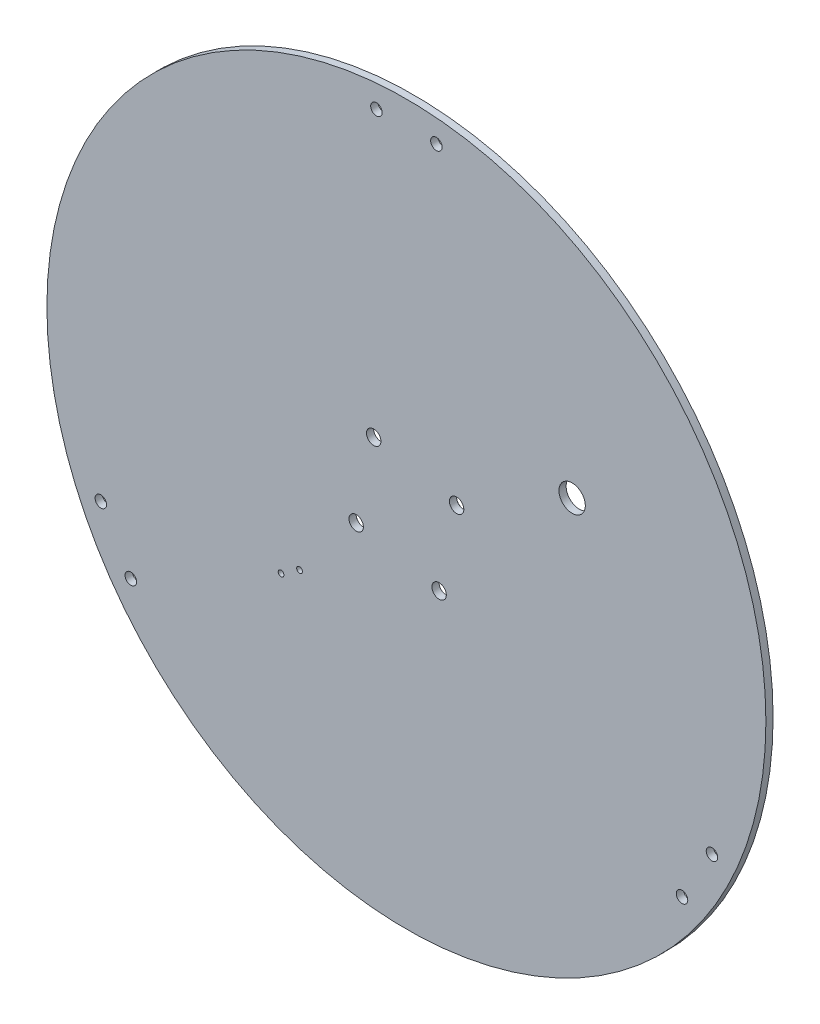
SolidWorks part; units mm, degrees
ref_plane "Front Plane" through (0, 0, 0) normal (0, 0, 1) x (1, 0, 0)
ref_plane "Top Plane" through (0, 0, 0) normal (0, 1, 0) x (1, 0, 0)
ref_plane "Right Plane" through (0, 0, 0) normal (1, 0, 0) x (0, 0, -1)
sketch "Sketch1" plane through (0, 0, 0) normal (0, 0, 1) x (1, 0, 0)
  line L0 (0, 0) -> (0, 140) construction
  line L1 (0, 140) -> (0, 150) construction
  line L2 (-12.5, 140) -> (12.5, 140) construction
  circle A0 centre (0, 0) radius 150
  circle A1 centre (12.5, 140) radius 2.4
  circle A2 centre (-12.5, 140) radius 2.4
  circle A3 centre (127.4936, -59.1747) radius 2.4
  circle A4 centre (114.9936, -80.8253) radius 2.4
  circle A5 centre (-114.9936, -80.8253) radius 2.4
  circle A6 centre (-127.4936, -59.1747) radius 2.4
  circle A7 centre (69.1451, 40.3483) radius 5.5
  circle A10 centre (-44.588, -42.5012) radius 1.2
  circle A11 centre (-52.288, -47.6012) radius 1.2
  point P9 (0, 140)
  point P21 (0, 0)
  dimension "D1" = 300
  dimension "D2" = 3
  dimension "D4" = 4.8
  dimension "D6" = 11
  dimension "D7" = 2.4
  dimension "D8" = 2.4
  dimension "D3" = 25
  dimension "D5" = 140
extrude "Boss-Extrude2" add sketch "Sketch1" along normal blind 3
sketch "Sketch2" plane through (0, 0, 0) normal (0, 0, -1) x (-1, 0, 0)
  circle A13 centre (-13.6439, -20.9486) radius 3.2 construction
  circle A14 centre (20.9486, -13.6439) radius 3.2 construction
  circle A15 centre (13.6439, 20.9486) radius 3.2 construction
  circle A16 centre (-20.9486, 13.6439) radius 3.2 construction
  circle A17 centre (-13.6439, -20.9486) radius 3.2
  circle A18 centre (20.9486, -13.6439) radius 3.2
  circle A19 centre (13.6439, 20.9486) radius 3.2
  circle A20 centre (-20.9486, 13.6439) radius 3.2
hole_wizard "Ø6.0mm Dowel Hole1" positions "Sketch8" profile "Sketch9" hole size "Ø6.0" standard "ANSI Metric" end condition through all
sketch "Sketch8" plane through (0, 0, 0) normal (0, 0, -1) x (-1, 0, 0)
  point P0 (-20.9486, 13.6439)
  point P3 (13.6439, 20.9486)
  point P6 (20.9486, -13.6439)
  point P9 (-13.6439, -20.9486)
sketch "Sketch9" plane through (20.9486, 13.6439, 0) normal (1, 0, 0) x (0, 1, 0)
  line L0 (0, 0) -> (0, 3)
  line L1 (0, 3) -> (3, 3)
  line L2 (3, 3) -> (3, 0.025)
  line L3 (3, 0.025) -> (3.025, 0)
  line L5 (3.025, 0) -> (0, 0)
  line L6 (-3, 0.025) -> (-3.025, 0) construction
  line L11 (0, -6.35) -> (0, 107.95) construction
  dimension "Thru Hole Dia." = 6
  dimension "Thru Hole Depth" = 3
  dimension "Near C'Sink Dia." = 6.05
  dimension "Near C'Sink Angle" = 90
